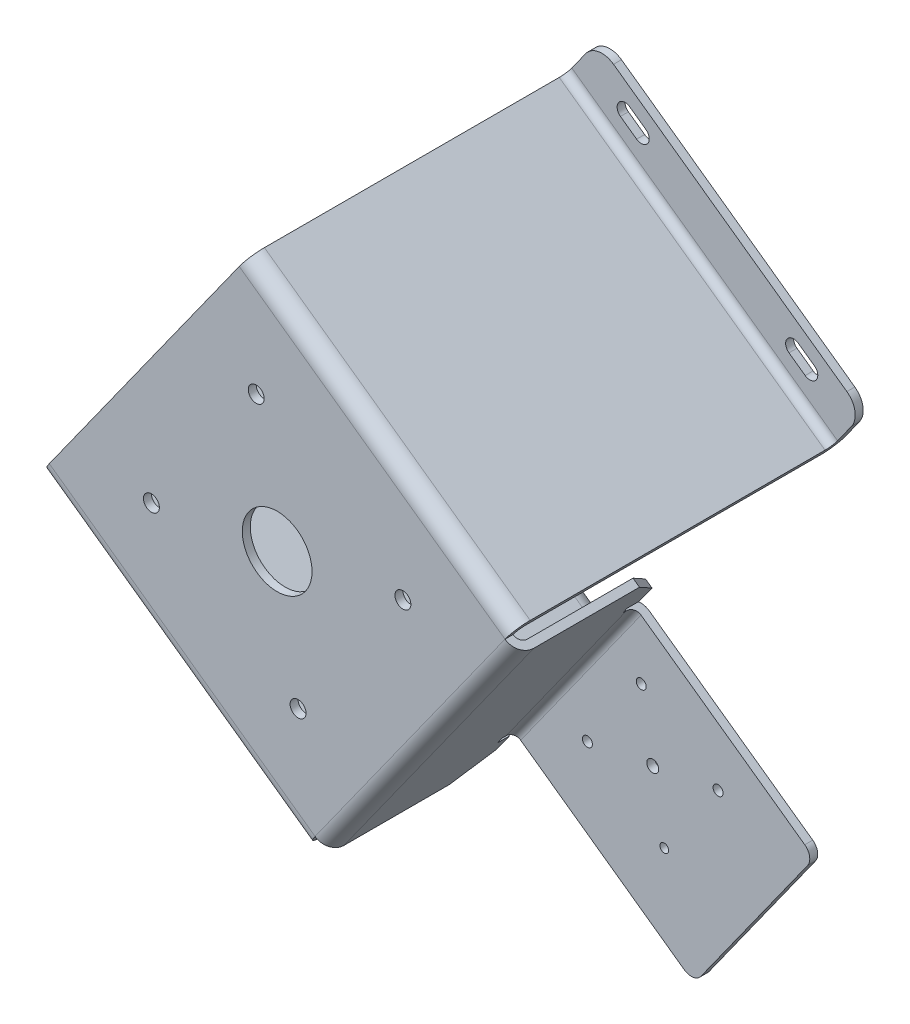
SolidWorks part; units mm, degrees
ref_plane "Front Plane" through (0, 0, 0) normal (0, 0, 1) x (1, 0, 0)
ref_plane "Top Plane" through (0, 0, 0) normal (0, 1, 0) x (1, 0, 0)
ref_plane "Right Plane" through (0, 0, 0) normal (1, 0, 0) x (0, 0, -1)
ref_plane "Plane1" through (73.224, -52.3283, 0) normal (0.8136, -0.5814, 0) x (0.5814, 0.8136, 0)
sketch "Sketch1" plane through (73.224, -52.3283, 0) normal (0.8136, -0.5814, 0) x (0.5814, 0.8136, 0)
  line L0 (-82, -57) -> (-67, -72)
  line L1 (-67, -72) -> (67, -72)
  line L2 (67, -72) -> (82, -57)
  line L3 (82, -57) -> (82, 4)
  line L4 (82, 4) -> (-82, 4)
  line L5 (-82, 4) -> (-82, -57)
  dimension "D1" = 135
  dimension "D2" = 135
  dimension "D3" = 134
  dimension "D4" = 21.2132
  dimension "D5" = 21.2132
  dimension "D6" = 61
extrude "Boss-Extrude1" add sketch "Sketch1" against normal blind 4
sketch "Sketch2" plane through (69.9696, -50.0026, 0) normal (-0.8136, 0.5814, 0) x (0, 0, 1)
  line L0 (4, 82) -> (4, -82)
  line L1 (4, -82) -> (0, -82)
  line L2 (0, -82) -> (0, 82)
  line L3 (0, 82) -> (4, 82)
extrude "Boss-Extrude2" add sketch "Sketch2" along normal blind 168
sketch "Sketch3" plane through (47.6769, 66.7152, 0) normal (0.5814, 0.8136, 0) x (-0.8136, 0.5814, 0)
  line L0 (82, 0) -> (-82, 0)
  line L1 (-82, 0) -> (-82, 4)
  line L2 (-82, 4) -> (82, 4)
  line L3 (82, 4) -> (82, 0)
extrude "Boss-Extrude3" add sketch "Sketch3" along normal blind 34
sketch "Sketch4" plane through (0, 0, 0) normal (0, 0, -1) x (-1, 0, 0)
  line L0 (-116.7178, 22.2927) -> (-134.1605, 46.7007)
  line L1 (-134.1605, 46.7007) -> (-0.7301, 142.0545)
  line L2 (-0.7301, 142.0545) -> (16.7126, 117.6465)
  line L3 (16.7126, 117.6465) -> (-116.7178, 22.2927)
extrude "Boss-Extrude4" add sketch "Sketch4" along normal blind 160
sketch "Sketch5" plane through (-47.6769, -66.7152, 0) normal (-0.5814, -0.8136, 0) x (0.8136, -0.5814, 0)
  line L0 (-82, 0) -> (-82, 4)
  line L1 (-82, 4) -> (82, 4)
  line L2 (82, 4) -> (82, 0)
  line L3 (82, 0) -> (-82, 0)
extrude "Boss-Extrude5" add sketch "Sketch5" along normal blind 34
sketch "Sketch6" plane through (0, 0, 0) normal (0, 0, -1) x (-1, 0, 0)
  line L0 (116.7178, -22.2927) -> (134.1605, -46.7007)
  line L1 (134.1605, -46.7007) -> (0.7301, -142.0545)
  line L2 (0.7301, -142.0545) -> (-16.7126, -117.6465)
  line L3 (-16.7126, -117.6465) -> (116.7178, -22.2927)
extrude "Boss-Extrude6" add sketch "Sketch6" along normal blind 160
sketch "Sketch7" plane through (69.9696, -50.0026, 0) normal (-0.8136, 0.5814, 0) x (0, 0, 1)
  line L0 (-72, 56) -> (-72, -56)
  line L1 (-72, -56) -> (-66, -56)
  line L2 (-66, -56) -> (-66, 56)
  line L3 (-66, 56) -> (-72, 56)
  dimension "D1" = 6
  dimension "D2" = 112
extrude "Cut-Extrude1" cut sketch "Sketch7" against normal through all
sketch "Sketch8" plane through (0, 0, -66) normal (0, 0, -1) x (-1, 0, 0)
  line L0 (-42.9899, -94.6355) -> (-103.4581, -10.0211)
  line L1 (-103.4581, -10.0211) -> (-100.2037, -7.6954)
  line L2 (-100.2037, -7.6954) -> (-39.7355, -92.3098)
  line L3 (-39.7355, -92.3098) -> (-42.9899, -94.6355)
extrude "Boss-Extrude7" add sketch "Sketch8" along normal blind 10
sketch "Sketch9" plane through (73.224, -52.3283, 0) normal (0.8136, -0.5814, 0) x (0, 0, -1)
  line L0 (76, 52) -> (76, -52)
  line L1 (76, -52) -> (72, -52)
  line L2 (72, -52) -> (72, 52)
  line L3 (72, 52) -> (76, 52)
extrude "Boss-Extrude8" add sketch "Sketch9" along normal blind 111
sketch "Sketch10" plane through (66.7152, -47.6769, 0) normal (0.8136, -0.5814, 0) x (0, 0, -1)
  line L0 (-4, -116) -> (156, -116)
  line L1 (156, -116) -> (156, -90)
  line L2 (156, -90) -> (-4, -90)
  line L3 (-4, -90) -> (-4, -116)
extrude "Cut-Extrude2" cut sketch "Sketch10" against normal through all
sketch "Sketch11" plane through (-66.7152, 47.6769, 0) normal (-0.8136, 0.5814, 0) x (0, 0, 1)
  line L0 (-156, 116) -> (-156, 90)
  line L1 (-156, 90) -> (4, 90)
  line L2 (4, 90) -> (4, 116)
  line L3 (4, 116) -> (-156, 116)
extrude "Cut-Extrude3" cut sketch "Sketch11" against normal through all
sketch "Sketch12" plane through (0, 0, -72) normal (0, 0, 1) x (1, 0, 0)
  line L0 (79.7674, -80.7737) -> (86.9065, -88.0878) construction
  line L1 (79.7674, -80.7737) -> (145.3649, -69.2071) construction
  line L2 (145.3649, -69.2071) -> (106.7829, -42.1916) construction
  line L7 (118.3495, -107.7892) -> (122.5924, -113.0754) construction
  line L8 (106.7829, -42.1916) -> (118.3495, -107.7892) construction
  line L9 (106.7829, -42.1916) -> (79.7674, -80.7737) construction
  line L10 (79.7674, -80.7737) -> (118.3495, -107.7892) construction
  line L11 (118.3495, -107.7892) -> (145.3649, -69.2071) construction
  line L12 (145.3649, -69.2071) -> (118.3495, -107.7892) construction
  line L13 (147.58, -77.3895) -> (145.3649, -69.2071) construction
  line L14 (111.894, -52.4019) -> (106.7829, -42.1916) construction
  circle A1 centre (112.5662, -74.9904) radius 3
  circle A10 centre (79.7674, -80.7737) radius 2.5
  circle A11 centre (118.3495, -107.7892) radius 2.1921
  circle A12 centre (145.3649, -69.2071) radius 2.5
  circle A13 centre (106.7829, -42.1916) radius 2.5
  point P5 (117.2432, -82.7386)
  dimension "D2" = 47.1
  dimension "D5" = 47.1
  dimension "D1" = 47.1
  dimension "D3" = 5
  dimension "D4" = 6
  dimension "D6" = 32.7988
  dimension "D7" = 32.7988
  dimension "D8" = 32.7988
  dimension "D9" = 32.7988
  dimension "D10" = 47.1
extrude "Cut-Extrude4" cut sketch "Sketch12" against normal through all
sketch "Sketch19" plane through (0, 0, -156) normal (0, 0, 1) x (1, 0, 0)
  line L0 (-12.3488, -115.3148) -> (-20.4848, -109.5006)
  line L1 (-25.1362, -116.0094) -> (-17.0002, -121.8236)
  line L2 (-0.7301, -142.0545) -> (-134.1605, -46.7007) construction
  line L3 (-67.4453, -94.3776) -> (-50.0026, -69.9696) construction
  line L4 (-116.7178, -22.2927) -> (16.7126, -117.6465) construction
  line L5 (-105.0991, -49.0323) -> (-96.9631, -54.8466)
  line L6 (-101.6145, -61.3554) -> (-109.7505, -55.5411)
  line L7 (-67.4453, -94.3776) -> (67.4453, 94.3776) construction
  line L8 (0.7301, 142.0545) -> (134.1605, 46.7007) construction
  line L9 (57.442, -41.0499) -> (-71.8322, 51.3336) construction
  line L10 (101.6145, 61.3554) -> (109.7505, 55.5411)
  line L11 (105.0991, 49.0323) -> (96.9631, 54.8466)
  line L12 (25.1362, 116.0094) -> (17.0002, 121.8236)
  line L13 (12.3488, 115.3148) -> (20.4848, 109.5006)
  arc A0 (-20.4848, -109.5006) -> (-25.1362, -116.0094) centre (-22.8105, -112.755) ccw
  arc A1 (-17.0002, -121.8236) -> (-12.3488, -115.3148) centre (-14.6745, -118.5692) ccw
  arc A2 (-109.7505, -55.5411) -> (-105.0991, -49.0323) centre (-107.4248, -52.2867) cw
  arc A3 (-96.9631, -54.8466) -> (-101.6145, -61.3554) centre (-99.2888, -58.101) cw
  arc A4 (109.7505, 55.5411) -> (105.0991, 49.0323) centre (107.4248, 52.2867) cw
  arc A5 (96.9631, 54.8466) -> (101.6145, 61.3554) centre (99.2888, 58.101) cw
  arc A6 (20.4848, 109.5006) -> (25.1362, 116.0094) centre (22.8105, 112.755) ccw
  arc A7 (17.0002, 121.8236) -> (12.3488, 115.3148) centre (14.6745, 118.5692) ccw
  dimension "D2" = 4
  dimension "D3" = 4
  dimension "D1" = 11
extrude "Cut-Extrude11" cut sketch "Sketch19" against normal through all
hole_wizard "Tap Drill for M33 Helicoil1" positions "Sketch22" profile "Sketch21" hole size "M33x3.5" standard "ANSI Metric"
sketch "Sketch22" plane through (0, 0, 0) normal (0, 0, -1) x (-1, 0, 0)
  point P0 (0, 0)
sketch "Sketch21" plane through (0, 0, 0) normal (1, 0, 0) x (0, 1, 0)
  line L0 (0, 0) -> (0, 35.5151)
  line L1 (0, 35.5151) -> (17.5, 25)
  line L2 (17.5, 25) -> (17.5, 0)
  line L5 (17.5, 0) -> (0, 0)
  line L10 (0, 35.5151) -> (-17.5, 25) construction
  line L11 (0, -6.35) -> (0, 107.95) construction
  dimension "Hole Dia." = 35
  dimension "Hole Depth" = 25
  dimension "Drill Angle" = 118
hole_wizard "Ø8.0 (8) Diameter Hole1" positions "Sketch24" profile "Sketch23" hole size "Ø8.0" standard "ANSI Metric" end condition through all
sketch "Sketch24" plane through (0, 0, 0) normal (0, 0, -1) x (-1, 0, 0)
  point P0 (10.507, 63.1316)
  point P1 (63.1316, -10.507)
  point P2 (-63.1316, 10.507)
  point P3 (-10.507, -63.1316)
sketch "Sketch23" plane through (-10.507, 63.1316, 0) normal (1, 0, 0) x (0, 1, 0)
  line L0 (0, 0) -> (0, 4)
  line L1 (0, 4) -> (4, 4)
  line L2 (4, 4) -> (4, 0)
  line L5 (4, 0) -> (0, 0)
  line L11 (0, -6.35) -> (0, 107.95) construction
  dimension "Thru Hole Dia." = 8
  dimension "Thru Hole Depth" = 4
fillet "Fillet1" radius 4 6 edges at (-52.3283, -73.224, -156) (50.0026, 69.9696, 0) (-50.0026, -69.9696, 0) (73.224, -52.3283, -72) (69.9696, -50.0026, 0) (52.3283, 73.224, -156) tangent propagation no
fillet "Fillet2" radius 6 2 edges at (193.7677, -74.5593, -74) (133.2994, -159.1737, -74) tangent propagation no
fillet "Fillet3" radius 8 6 edges at (-50.0026, -69.9696, -160) (-52.3283, -73.224, 4) (73.224, -52.3283, 4) (69.9696, -50.0026, -76) (50.0026, 69.9696, -160) (52.3283, 73.224, 4) tangent propagation no
fillet "Fillet4" radius 10 4 edges at (-0.7301, -142.0545, -158) (134.1605, 46.7007, -158) (0.7301, 142.0545, -158) (-134.1605, -46.7007, -158) tangent propagation no
